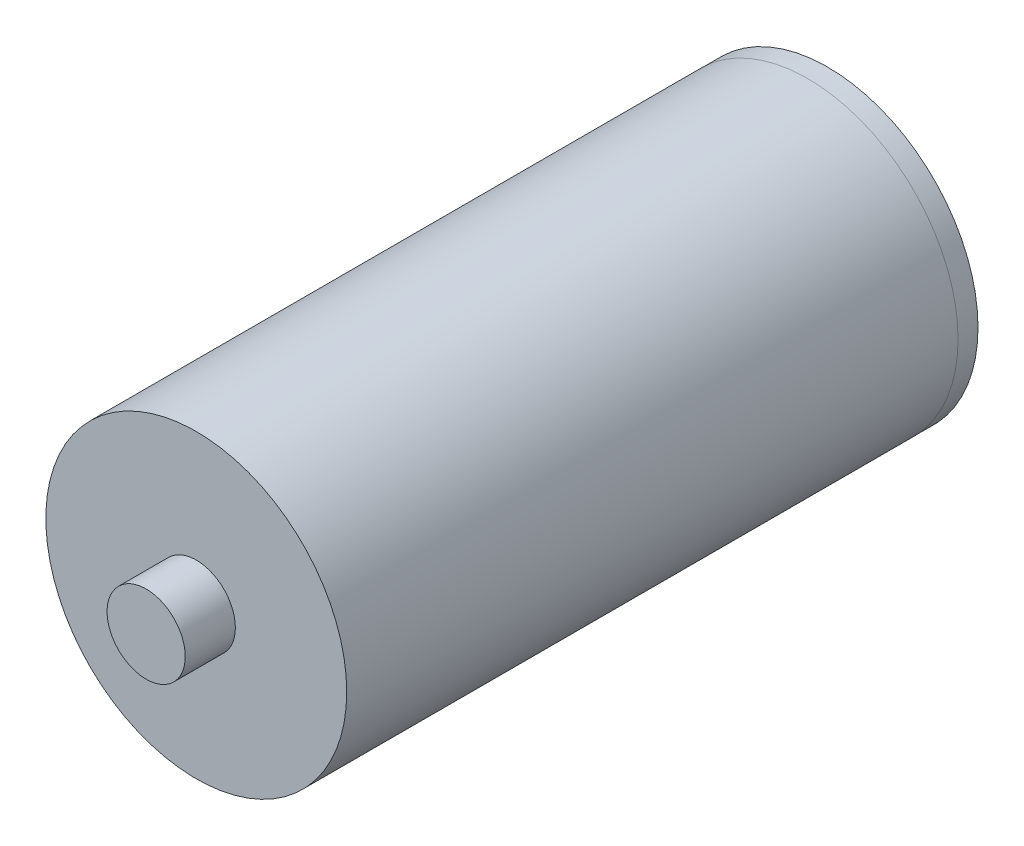
SolidWorks part; units mm, degrees
ref_plane "Front Plane" through (0, 0, 0) normal (0, 0, 1) x (1, 0, 0)
ref_plane "Top Plane" through (0, 0, 0) normal (0, 1, 0) x (1, 0, 0)
ref_plane "Right Plane" through (0, 0, 0) normal (1, 0, 0) x (0, 0, -1)
sketch "Sketch1" plane through (0, 0, 0) normal (0, 0, 1) x (1, 0, 0)
  line L0 (-1.0292, 0.3613) -> (2.4308, -1.0621) construction
  line L1 (-1.0292, 0.3613) -> (2.4308, 0.3613)
  line L2 (-1.0292, 0.3613) -> (-1.0292, -1.0621) construction
  line L3 (-1.0292, -1.0621) -> (2.4308, -1.0621)
  line L4 (2.4308, 0.3613) -> (2.4308, -1.0621) construction
  line L5 (-1.0292, -1.0621) -> (2.4308, 0.3613) construction
  line L6 (0.7008, -0.3504) -> (0.7008, 1.1496) construction
  line L8 (0.7008, -0.3504) -> (0.7008, -1.8504) construction
  line L11 (0.7008, 1.1496) -> (-1.2992, 1.1496)
  line L12 (0.7008, 1.1496) -> (2.7008, 1.1496)
  line L13 (2.7008, -1.8504) -> (-1.2992, -1.8504)
  arc A0 (-1.0292, -1.0621) -> (-1.0292, 0.3613) centre (0.7008, -0.3504) cw
  arc A1 (2.4308, 0.3613) -> (2.4308, -1.0621) centre (0.7008, -0.3504) cw
  arc A3 (-1.2992, -1.8504) -> (-1.2992, 1.1496) centre (0.7008, -0.3504) cw
  arc A4 (2.7008, -1.8504) -> (2.6894, 1.1646) centre (0.7008, -0.3504) ccw
  circle A5 centre (0.7008, -0.3504) radius 3.5
  point P14 (0.7008, -1.8504)
  dimension "D2" = 1
  dimension "D1" = 3.46
  dimension "D3" = 1.5
  dimension "D4" = 1.5
extrude "Boss-Extrude1" add sketch "Sketch1" along normal blind 3.25 contours L1 A1 L3 A0 | A5 region at (1.7008, 1.0913, 0)
sketch "Sketch3" plane through (0, 0, 3.25) normal (0, 0, 1) x (1, 0, 0)
  circle A0 centre (0.7008, -0.3504) radius 15
  dimension "D1" = 30
extrude "Boss-Extrude2" add sketch "Sketch3" along normal blind 2 contours A0
sketch "Sketch4" plane through (0, 0, 5.25) normal (0, 0, 1) x (1, 0, 0)
  circle A0 centre (0.7008, -0.3504) radius 15.0111
  circle A1 centre (0.7008, -0.3504) radius 13.0111
  dimension "D1" = 2
extrude "Boss-Extrude3" add sketch "Sketch4" along normal blind 59
sketch "Sketch5" plane through (0, 0, 3.25) normal (0, 0, -1) x (-1, 0, 0)
  line L2 (-2.7008, -1.8504) -> (1.2992, -1.8504)
  line L3 (1.2992, 1.1496) -> (-2.7008, 1.1496)
  line L4 (-2.7008, -1.8504) -> (1.2992, -1.8504)
  line L5 (1.2992, 1.1496) -> (-2.7008, 1.1496)
  arc A2 (-2.7008, 1.1496) -> (-2.7008, -1.8504) centre (-0.7008, -0.3504) ccw
  arc A3 (1.2992, -1.8504) -> (1.2992, 1.1496) centre (-0.7008, -0.3504) ccw
  arc A4 (-2.7008, 1.1496) -> (-2.7008, -1.8504) centre (-0.7008, -0.3504) ccw
  arc A5 (1.2992, -1.8504) -> (1.2992, 1.1496) centre (-0.7008, -0.3504) ccw
  dimension "D1" = 0
extrude "Cut-Extrude1" cut sketch "Sketch5" against normal blind 5
sketch "Sketch6" plane through (0, 0, 64.25) normal (0, 0, 1) x (1, 0, 0)
  circle A0 centre (0.7008, -0.3504) radius 15.0111
extrude "Boss-Extrude4" add sketch "Sketch6" along normal blind 2
sketch "Sketch7" plane through (0, 0, 66.25) normal (0, 0, 1) x (1, 0, 0)
  line L0 (0.7008, 14.6607) -> (0.7008, -15.3615) construction
  circle A0 centre (0.7008, -0.3504) radius 15.0111 construction
  circle A1 centre (0.7008, -0.3504) radius 3.9
  dimension "D1" = 7.8
extrude "Boss-Extrude5" add sketch "Sketch7" along normal blind 5
